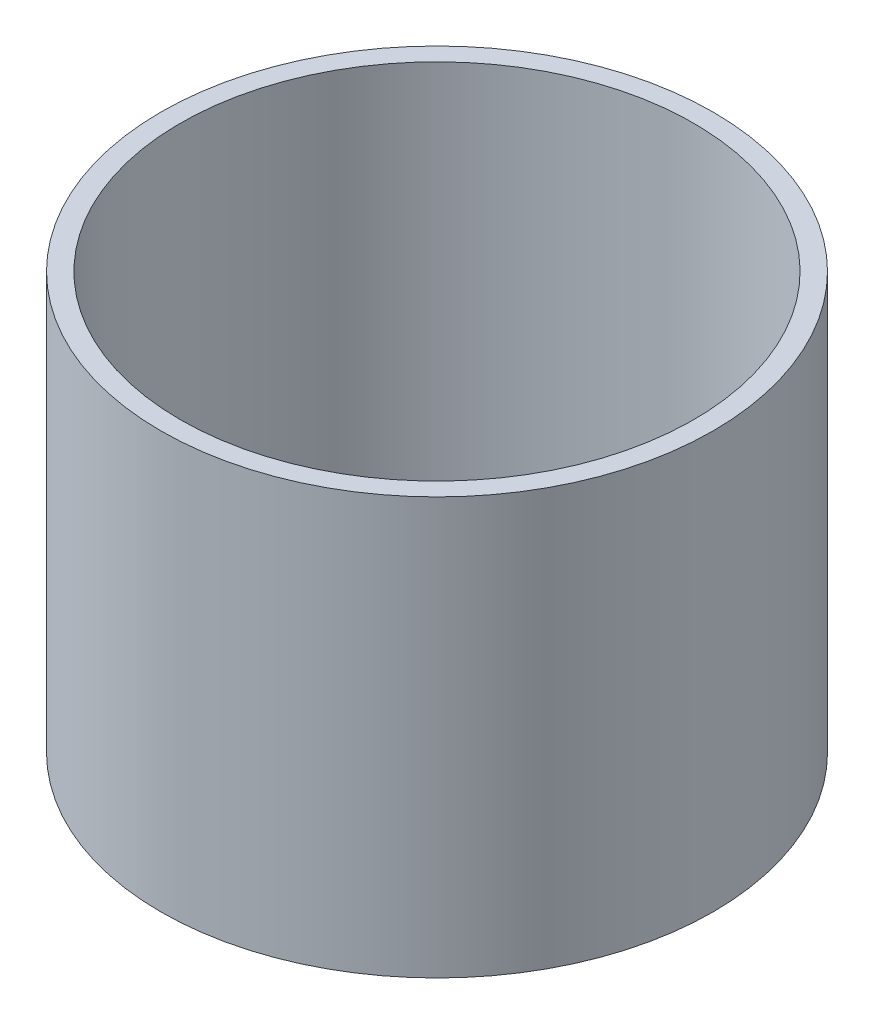
SolidWorks part; units mm, degrees
ref_plane "Front Plane" through (0, 0, 0) normal (0, 0, 1) x (1, 0, 0)
ref_plane "Top Plane" through (0, 0, 0) normal (0, 1, 0) x (1, 0, 0)
ref_plane "Right Plane" through (0, 0, 0) normal (1, 0, 0) x (0, 0, -1)
sketch "Sketch1" plane through (0, 0, 0) normal (0, 1, 0) x (1, 0, 0)
  circle A1 centre (0, 0) radius 67.31
  circle A2 centre (0, 0) radius 72.39
  dimension "D1" = 134.62
  dimension "D3" = 5.08
extrude "Boss-Extrude1" add sketch "Sketch1" along normal blind 104.14
sketch "Sketch2" plane through (0, 0, 0) normal (0, -1, 0) x (1, 0, 0)
  circle A0 centre (0, 0) radius 72.39
  circle A1 centre (0, 48.26) radius 3.3782
  circle A2 centre (48.26, 0) radius 3.3782
  circle A3 centre (0, -48.26) radius 3.3782
  circle A4 centre (-48.26, 0) radius 3.3782
  circle A5 centre (0, 0) radius 72.39 construction
  point P14 (0, 0)
  dimension "D1" = 6.7564
  dimension "D2" = 48.26
  dimension "D3" = 4
extrude "Boss-Extrude2" add sketch "Sketch2" along normal blind 5.08
